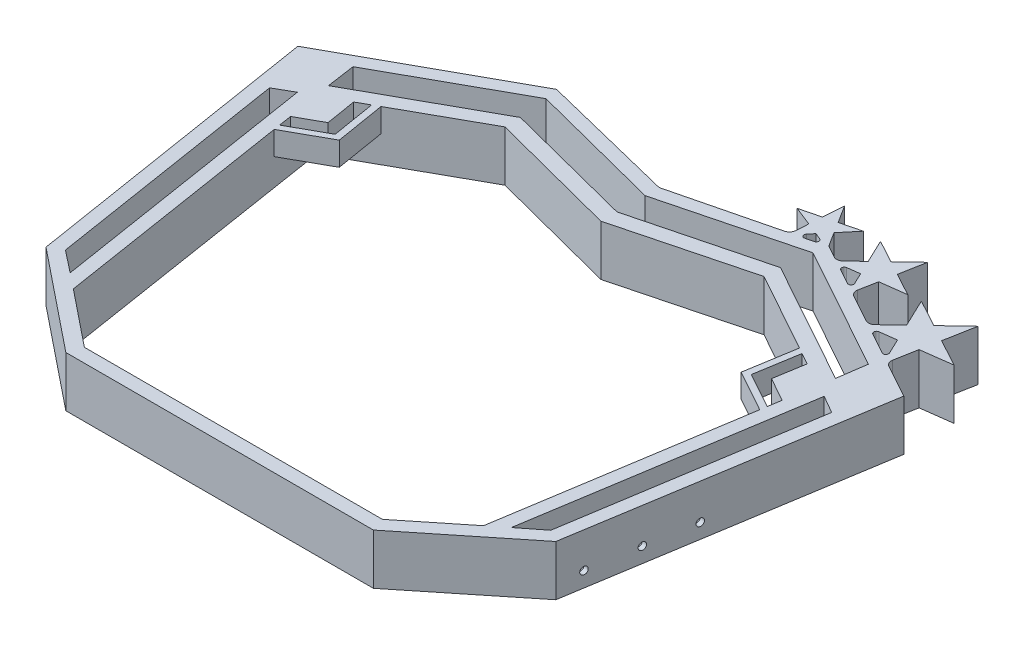
SolidWorks part; units mm, degrees
ref_plane "前视基准面" through (0, 0, 0) normal (0, 0, 1) x (1, 0, 0)
ref_plane "上视基准面" through (0, 0, 0) normal (0, 1, 0) x (1, 0, 0)
ref_plane "右视基准面" through (0, 0, 0) normal (1, 0, 0) x (0, 0, -1)
other "Configuration Table"
sketch "草图1" plane through (0, 0, 0) normal (0, 1, 0) x (1, 0, 0)
  line L0 (155.7811, 255.7193) -> (788.8641, 255.7193) construction
  line L1 (0, 0) -> (180, 0) construction
  line L2 (0, 0) -> (14.2759, -89.0996)
  line L3 (14.2759, -89.0996) -> (44.3217, -113.2519)
  line L5 (90, -113.2519) -> (90, 0) construction
  line L6 (0, 0) -> (49.5195, 27.3202)
  line L7 (49.5195, 27.3202) -> (90, 17.2996)
  line L8 (90, 17.2996) -> (90, 0) construction
  line L9 (90, 13.1373) -> (50.3269, 23.3566)
  line L10 (50.3269, 23.3566) -> (13.4578, 2.9247)
  line L11 (13.4578, 2.9247) -> (14.6874, -5.6027)
  line L12 (14.6874, -5.6027) -> (51.3648, 14.7229)
  line L13 (51.3648, 14.7229) -> (90, 4.771)
  line L14 (11.766, -11.9028) -> (6.5026, -14.9209)
  line L15 (6.5026, -14.9209) -> (17.9121, -86.9655)
  line L16 (17.9121, -86.9655) -> (24.4693, -92.1171)
  line L17 (24.4693, -92.1171) -> (11.766, -11.9028)
  line L18 (90, 0) -> (51.5113, 10)
  line L19 (51.5113, 10) -> (22.6331, -6.0642)
  line L20 (22.6331, -6.0642) -> (24.1321, -15.1776)
  line L21 (24.1321, -15.1776) -> (16.9777, -19.1574)
  line L22 (16.9777, -19.1574) -> (29.0746, -95.7713)
  line L23 (29.0746, -95.7713) -> (45.7277, -109.1591)
  line L25 (27.8598, -3.1567) -> (30.3034, -18.0117)
  line L26 (30.3034, -18.0117) -> (17.8873, -24.9184)
  line L27 (26.0584, -4.1588) -> (28.188, -17.1051)
  line L28 (28.188, -17.1051) -> (17.585, -23.0033)
  line L29 (44.3217, -113.2519) -> (135.6783, -113.2519)
  line L30 (45.7277, -109.1591) -> (134.2723, -109.1591)
  line L31 (151.812, -17.1051) -> (162.415, -23.0033)
  line L32 (153.9416, -4.1588) -> (151.812, -17.1051)
  line L33 (149.6966, -18.0117) -> (162.1127, -24.9184)
  line L34 (152.1402, -3.1567) -> (149.6966, -18.0117)
  line L35 (150.9254, -95.7713) -> (134.2723, -109.1591)
  line L36 (163.0223, -19.1574) -> (150.9254, -95.7713)
  line L37 (155.8679, -15.1776) -> (163.0223, -19.1574)
  line L38 (157.3669, -6.0642) -> (155.8679, -15.1776)
  line L39 (128.4887, 10) -> (157.3669, -6.0642)
  line L40 (90, 0) -> (128.4887, 10)
  line L41 (155.5307, -92.1171) -> (168.234, -11.9028)
  line L42 (162.0879, -86.9655) -> (155.5307, -92.1171)
  line L43 (173.4974, -14.9209) -> (162.0879, -86.9655)
  line L44 (168.234, -11.9028) -> (173.4974, -14.9209)
  line L45 (128.6352, 14.7229) -> (90, 4.771)
  line L46 (165.3126, -5.6027) -> (128.6352, 14.7229)
  line L47 (166.5422, 2.9247) -> (165.3126, -5.6027)
  line L48 (129.6731, 23.3566) -> (166.5422, 2.9247)
  line L49 (90, 13.1373) -> (129.6731, 23.3566)
  line L50 (130.4805, 27.3202) -> (90, 17.2996)
  line L51 (180, 0) -> (130.4805, 27.3202)
  line L52 (165.7241, -89.0996) -> (135.6783, -113.2519)
  line L53 (180, 0) -> (165.7241, -89.0996)
  line L54 (22.6331, -6.0642) -> (15.5339, -10.0133)
  line L55 (15.5339, -10.0133) -> (16.9777, -19.1574)
  line L56 (157.3669, -6.0642) -> (164.4661, -10.0133)
  line L57 (164.4661, -10.0133) -> (163.0223, -19.1574)
  point P38 (90, -109.1591)
  point P41 (90, -109.1591)
  dimension "D1" = 90
  dimension "D2" = 113.2519
  dimension "D3" = 89.0996
  dimension "D4" = 75.7241
  dimension "D5" = 27.3202
  dimension "D6" = 45.6783
  dimension "D7" = 40.4805
  dimension "D8" = 17.2996
  dimension "D9" = 4.1623
  dimension "D10" = 8.3663
  dimension "D11" = 39.6731
  dimension "D12" = 23.3566
  dimension "D13" = 136.561
  dimension "D14" = 76.5422
  dimension "D15" = 8.6155
  dimension "D16" = 110.789
  dimension "D17" = 78.234
  dimension "D18" = 6.0673
  dimension "D19" = 69.168
  dimension "D20" = 72.0879
  dimension "D21" = 65.5307
  dimension "D22" = 11.9028
  dimension "D23" = 92.1171
  dimension "D24" = 44.2723
  dimension "D25" = 60.9254
  dimension "D26" = 73.0223
  dimension "D27" = 67.3669
  dimension "D28" = 38.4887
  dimension "D29" = 65.8679
  dimension "D30" = 109.1591
  dimension "D31" = 95.7713
  dimension "D32" = 19.1574
  dimension "D33" = 6.0642
  dimension "D34" = 10
  dimension "D35" = 59.6966
  dimension "D36" = 61.812
  dimension "D37" = 18.0117
  dimension "D38" = 17.1051
extrude "凸台-拉伸1" add sketch "草图1" along normal blind 15 contours L7 L6 L2 L3 L17 L16 L15 L14 L18 L23 L22 L21 L20 L19 L9 L13 L12 L11 region at (25.863, 0, -11.6604)
extrude "凸台-拉伸3" add sketch "草图1<4>" along normal up to surface (15 mm away) from offset 8 contours L57 L56 L38 L37 | L39 L34 L33 L36 L31 L32 | L54 L55 L21 L20 | L27 L28 L22 L26 L25 L19 region at (28.8329, 0, 10.6251) region at (152.9183, 0, 3.878) region at (19.8202, 0, 12.609) region at (160.1798, 0, 12.609) up to face at (90, 15, 36.9737)
sketch "草图1<4>" plane through (0, 0, 0) normal (0, 1, 0) x (1, 0, 0) same geometry as "草图1"
sketch "草图3" plane through (0, 0, 0) normal (0, 1, 0) x (1, 0, 0)
  line L23 (130.8951, 26.4295) -> (131.5696, 36.4067) construction
  line L24 (131.5696, 36.4067) -> (122.2891, 40.1314) construction
  line L25 (122.2891, 40.1314) -> (115.8789, 32.4561) construction
  line L26 (115.8789, 32.4561) -> (121.1977, 23.9879) construction
  line L27 (121.1977, 23.9879) -> (130.8951, 26.4295) construction
  line L28 (115.8789, 32.4561) -> (121.8722, 33.9651)
  line L29 (131.5696, 36.4067) -> (127.6079, 31.6632)
  line L30 (121.1977, 23.9879) -> (121.6146, 30.1541)
  line L31 (122.2891, 40.1314) -> (125.5763, 34.8977)
  line L32 (130.8951, 26.4295) -> (125.1594, 28.7315)
  line L35 (117.0279, 23.9692) -> (117.2721, 22.9995) construction
  line L36 (125.5763, 34.8977) -> (131.5696, 36.4067)
  line L37 (121.8722, 33.9651) -> (122.2891, 40.1314)
  line L38 (127.6079, 31.6632) -> (130.8951, 26.4295)
  line L39 (125.1594, 28.7315) -> (121.1977, 23.9879)
  line L40 (121.6146, 30.1541) -> (115.8789, 32.4561)
  circle A0 centre (124.3661, 31.8823) radius 8.5065 construction
  dimension "D1" = 10
  dimension "D2" = 1
sketch "草图4" plane through (0, 0, 0) normal (0, 1, 0) x (1, 0, 0)
  line L0 (158.1923, 27.0229) -> (179.5133, 15.4266)
  line L1 (168.6252, 5.1092) -> (179.5133, 15.4266) construction
  line L2 (179.5133, 15.4266) -> (173.0654, 28.97) construction
  line L3 (173.0654, 28.97) -> (158.1923, 27.0229) construction
  line L4 (158.1923, 27.0229) -> (155.4481, 12.2761) construction
  line L5 (155.4481, 12.2761) -> (168.6252, 5.1092) construction
  line L6 (179.5133, 15.4266) -> (155.4481, 12.2761)
  line L7 (155.4481, 12.2761) -> (173.0654, 28.97)
  line L8 (173.0654, 28.97) -> (168.6252, 5.1092)
  line L9 (168.6252, 5.1092) -> (158.1923, 27.0229)
  line L11 (172.3465, 4.1723) -> (171.8687, 3.2938) construction
  circle A0 centre (166.9689, 17.761) radius 12.7598 construction
  dimension "D1" = 15
  dimension "D3" = 1
sketch "草图5" plane through (0, 0, 0) normal (0, 1, 0) x (1, 0, 0)
  line L0 (136.7439, 36.3304) -> (154.5114, 26.6668)
  line L1 (145.438, 18.0689) -> (154.5114, 26.6668) construction
  line L2 (154.5114, 26.6668) -> (149.1381, 37.953) construction
  line L3 (149.1381, 37.953) -> (136.7439, 36.3304) construction
  line L4 (136.7439, 36.3304) -> (134.4571, 24.0413) construction
  line L5 (134.4571, 24.0413) -> (145.438, 18.0689) construction
  line L6 (154.5114, 26.6668) -> (134.4571, 24.0413)
  line L7 (134.4571, 24.0413) -> (149.1381, 37.953)
  line L8 (149.1381, 37.953) -> (145.438, 18.0689)
  line L9 (145.438, 18.0689) -> (136.7439, 36.3304)
  line L11 (132.0052, 26.4978) -> (131.5274, 25.6193) construction
  circle A0 centre (144.0577, 28.6121) radius 10.6331 construction
  dimension "D1" = 12.5
  dimension "D3" = 1
extrude "凸台-拉伸4" add sketch "草图3" along normal up to surface (15 mm away) up to face at (90, 15, 37.0796)
extrude "凸台-拉伸5" add sketch "草图4" along normal up to surface (15 mm away) contours L9 L6 L8 L0 L7 | L8 L7 L0 | L0 L8 L6 | L9 L8 L6 | L6 L9 L7 | L9 L7 L0 region at (162.2353, 0, -22.7563) region at (170.257, 0, -23.8065) region at (166.9689, 0, -17.761) region at (160.7552, 0, -14.8027) region at (173.7346, 0, -16.5019) region at (167.8622, 0, -10.9373) up to face at (125.6035, 15, -27.0224)
extrude "凸台-拉伸6" add sketch "草图5" along normal up to surface (15 mm away) contours L9 L6 L8 L0 L7 | L9 L7 L0 | L8 L7 L0 | L0 L8 L6 | L9 L8 L6 | L6 L9 L7 region at (140.113, 0, -32.7749) region at (146.7978, 0, -33.6501) region at (144.0577, 0, -28.6121) region at (138.8796, 0, -26.1469) region at (149.6958, 0, -27.5629) region at (144.8021, 0, -22.9257) up to face at (163.2733, 15, -10.8967)
fillet "圆角1" radius 2 6 edges at (168.822, 7.5, -6.1669) (145.6066, 7.5, -18.975) (156.2947, 7.5, -13.0783) (135.1807, 7.5, -24.7271) (130.3551, 7.5, -27.2891) (121.2688, 7.5, -25.0399)
fillet "圆角2" radius 0.8 6 edges at (167.8721, 7.5, -6.691) (144.7928, 7.5, -19.424) (129.3643, 7.5, -27.0439) (157.3076, 7.5, -12.5195) (136.0464, 7.5, -24.2494) (122.2868, 7.5, -25.2919)
sketch "草图6" plane through (0, 0, 0) normal (0, 1, 0) x (1, 0, 0)
  line L11 (164.4661, -10.0133) -> (128.4887, 10)
  line L12 (128.4887, 10) -> (90, 0)
  line L13 (90, 0) -> (51.5113, 10)
  line L14 (51.5113, 10) -> (15.5339, -10.0133)
  line L15 (15.5339, -10.0133) -> (29.0746, -95.7713)
  line L16 (29.0746, -95.7713) -> (45.7277, -109.1591)
  line L17 (45.7277, -109.1591) -> (134.2723, -109.1591)
  line L18 (134.2723, -109.1591) -> (150.9254, -95.7713)
  line L19 (150.9254, -95.7713) -> (164.4661, -10.0133)
  line L20 (164.4661, -10.0133) -> (128.4887, 10)
  line L21 (128.4887, 10) -> (90, 0)
  line L22 (90, 0) -> (51.5113, 10)
  line L23 (51.5113, 10) -> (15.5339, -10.0133)
  line L24 (15.5339, -10.0133) -> (29.0746, -95.7713)
  line L25 (29.0746, -95.7713) -> (45.7277, -109.1591)
  line L26 (45.7277, -109.1591) -> (134.2723, -109.1591)
  line L27 (134.2723, -109.1591) -> (150.9254, -95.7713)
  line L28 (150.9254, -95.7713) -> (164.4661, -10.0133)
  dimension "D1" = 0
sketch "草图7" plane through (0, 0, 0) normal (-0.9874, 0, 0.1582) x (0.1582, 0, 0.9874)
  circle A0 centre (52.8446, 4.5) radius 1.2 construction
  circle A1 centre (82.8446, 4.5) radius 1.2 construction
  circle A2 centre (67.8446, 4.5) radius 1.2 construction
  circle A3 centre (52.8446, 4.5) radius 1.2 construction
  circle A4 centre (82.8446, 4.5) radius 1.2 construction
  circle A5 centre (67.8446, 4.5) radius 1.2 construction
  point P10 (52.8446, 4.5)
  point P11 (67.8446, 4.5)
  point P12 (82.8446, 4.5)
hole_wizard "Ø2.0mm 暗销孔1" positions "草图7" profile "草图8" hole size "Ø2.0" standard "GB"
sketch "草图8" plane through (13.1066, 4.5, 81.8012) normal (0, 1, 0) x (0.1582, 0, 0.9874)
  line L0 (0, 0) -> (0, 2.1609)
  line L1 (0, 2.1609) -> (1.1, 1.5)
  line L2 (1.1, 1.5) -> (1.1, 0)
  line L5 (1.1, 0) -> (0, 0)
  line L10 (0, 2.1609) -> (-1.1, 1.5) construction
  line L11 (0, -6.35) -> (0, 107.95) construction
  dimension "孔直径" = 2.2
  dimension "孔深度" = 1.5
  dimension "导头角度" = 118
sketch "草图9" plane through (175.4947, 0, 28.1185) normal (0.9874, 0, 0.1582) x (0.1582, 0, -0.9874)
  circle A0 centre (-54.3674, 4.5) radius 1.2 construction
  circle A1 centre (-39.3674, 4.5) radius 1.2 construction
  circle A2 centre (-24.3674, 4.5) radius 1.2 construction
  circle A3 centre (-54.3674, 4.5) radius 1.2 construction
  circle A4 centre (-39.3674, 4.5) radius 1.2 construction
  circle A5 centre (-24.3674, 4.5) radius 1.2 construction
  point P9 (-39.3224, 4.5122)
  point P10 (-24.3109, 4.4094)
  point P11 (-54.4622, 4.481)
hole_wizard "Ø2.0mm 暗销孔2" positions "草图9" profile "草图10" hole size "Ø2.0" standard "GB"
sketch "草图10" plane through (166.8785, 4.481, 81.8948) normal (0, 1, 0) x (0.1582, 0, -0.9874)
  line L0 (0, 0) -> (0, 2.1609)
  line L1 (0, 2.1609) -> (1.1, 1.5)
  line L2 (1.1, 1.5) -> (1.1, 0)
  line L5 (1.1, 0) -> (0, 0)
  line L10 (0, 2.1609) -> (-1.1, 1.5) construction
  line L11 (0, -6.35) -> (0, 107.95) construction
  dimension "孔直径" = 2.2
  dimension "孔深度" = 1.5
  dimension "导头角度" = 118
